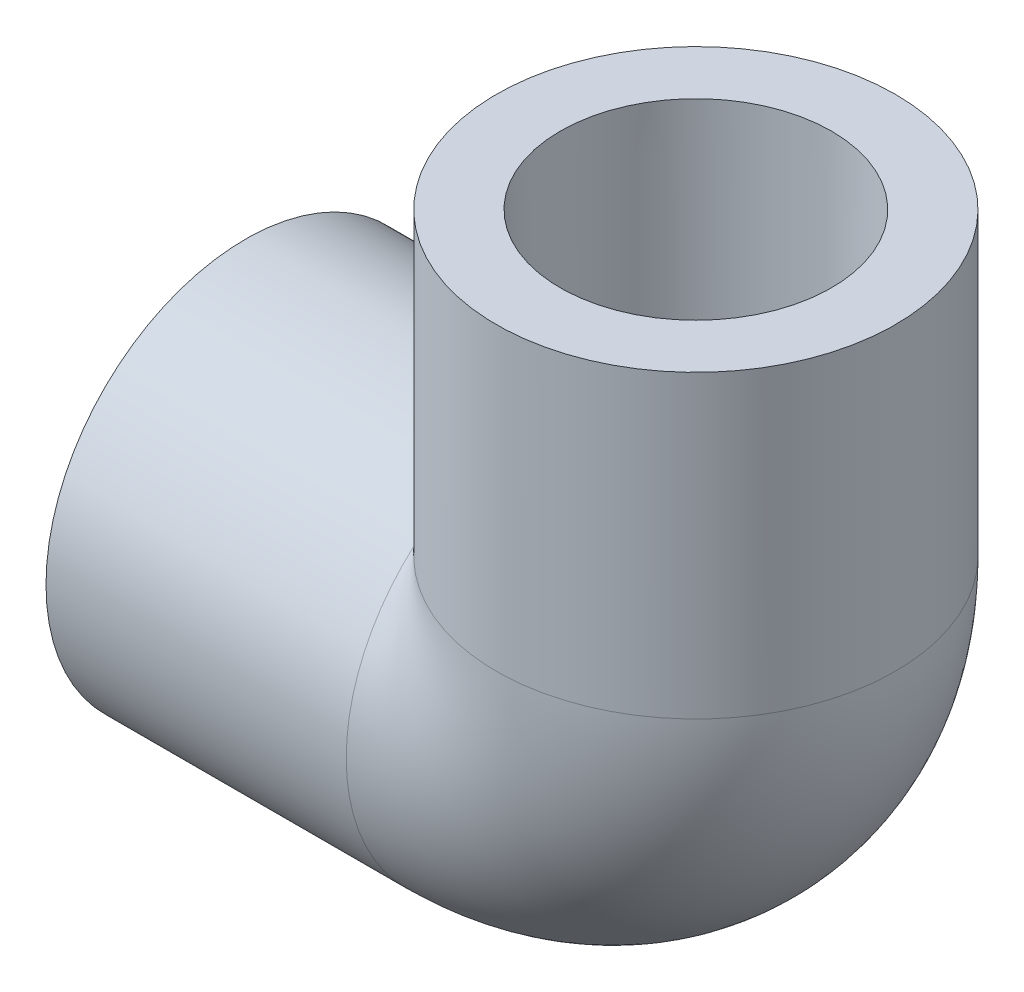
SolidWorks part; units mm, degrees
ref_plane "Front Plane" through (0, 0, 0) normal (0, 0, 1) x (1, 0, 0)
ref_plane "Top Plane" through (0, 0, 0) normal (0, 1, 0) x (1, 0, 0)
ref_plane "Right Plane" through (0, 0, 0) normal (1, 0, 0) x (0, 0, -1)
sketch "Sketch0" plane through (0, 0, 0) normal (0, 0, 1) x (1, 0, 0)
  line L0 (-28.956, 0) -> (0, 0) construction
  line L1 (0, 0) -> (0, 28.956) construction
  line L2 (-9.652, 0) -> (0, 0) construction
  line L3 (0, 0) -> (0, 9.652) construction
  line L4 (-28.956, 12.827) -> (-28.956, -12.827) construction
  line L5 (-9.652, 8.5217) -> (-28.956, 8.7249) construction
  line L6 (-9.652, 8.5217) -> (-9.652, -8.5217) construction
  line L7 (-9.652, -8.5217) -> (-28.956, -8.7249) construction
  line L8 (-28.956, 8.7249) -> (-28.956, -8.7249) construction
  line L9 (-12.827, 28.956) -> (12.827, 28.956) construction
  line L10 (-8.7249, 28.956) -> (8.7249, 28.956) construction
  line L11 (8.7249, 28.956) -> (8.5217, 9.652) construction
  line L12 (8.5217, 9.652) -> (-8.5217, 9.652) construction
  line L13 (-8.5217, 9.652) -> (-8.7249, 28.956) construction
  line L14 (-9.652, 5.3721) -> (-9.652, -5.3721) construction
  line L18 (-5.3721, 9.652) -> (5.3721, 9.652) construction
  dimension "H" = 28.956
  dimension "G" = 9.652
  dimension "M" = 25.654
  dimension "OD A" = 17.4498
  dimension "OD B" = 17.0434
  dimension "ID" = 10.7442
sketch "Sketch1" plane through (0, 0, 0) normal (0, 0, 1) x (1, 0, 0)
  line L0 (-28.956, 0) -> (0, 0) construction
  line L1 (-28.956, 0) -> (0, 0) construction
  line L3 (-28.956, -12.827) -> (-9.652, -12.827)
  line L4 (-28.956, -12.827) -> (-28.956, -8.7249)
  line L5 (-28.956, -8.7249) -> (-9.652, -8.5217)
  line L6 (-9.652, -12.827) -> (-9.652, -8.5217)
revolve "Revolve1" add sketch "Sketch1" angle 360 about L1
sketch "Sketch2" plane through (0, 0, 0) normal (0, 0, 1) x (1, 0, 0)
  line L0 (8.7249, 28.956) -> (8.5217, 9.652)
  line L1 (8.5217, 9.652) -> (12.827, 9.652)
  line L2 (12.827, 9.652) -> (12.827, 28.956)
  line L3 (12.827, 28.956) -> (8.7249, 28.956)
  line L4 (0, 0) -> (0, 28.956) construction
  line L5 (0, 0) -> (0, 28.956) construction
revolve "Revolve2" add sketch "Sketch2" angle 360 about L5
sketch "Sketch3" plane through (-9.652, 0, 0) normal (1, 0, 0) x (0, 0, -1)
  circle A0 centre (0, 0) radius 5.3721
  circle A1 centre (0, 0) radius 12.827
sketch "Sketch4" plane through (0, 0, 0) normal (0, 0, 1) x (1, 0, 0)
  line L0 (-28.956, 0) -> (0, 0) construction
  line L1 (0, 0) -> (0, 28.956) construction
  line L2 (-28.956, 0) -> (-9.652, 0) construction
  line L3 (0, 9.652) -> (0, 28.956) construction
  arc A0 (-9.652, 0) -> (0, 9.652) centre (-9.652, 9.652) ccw
sweep "Sweep1" add profiles "Sketch3" path "Sketch4"
